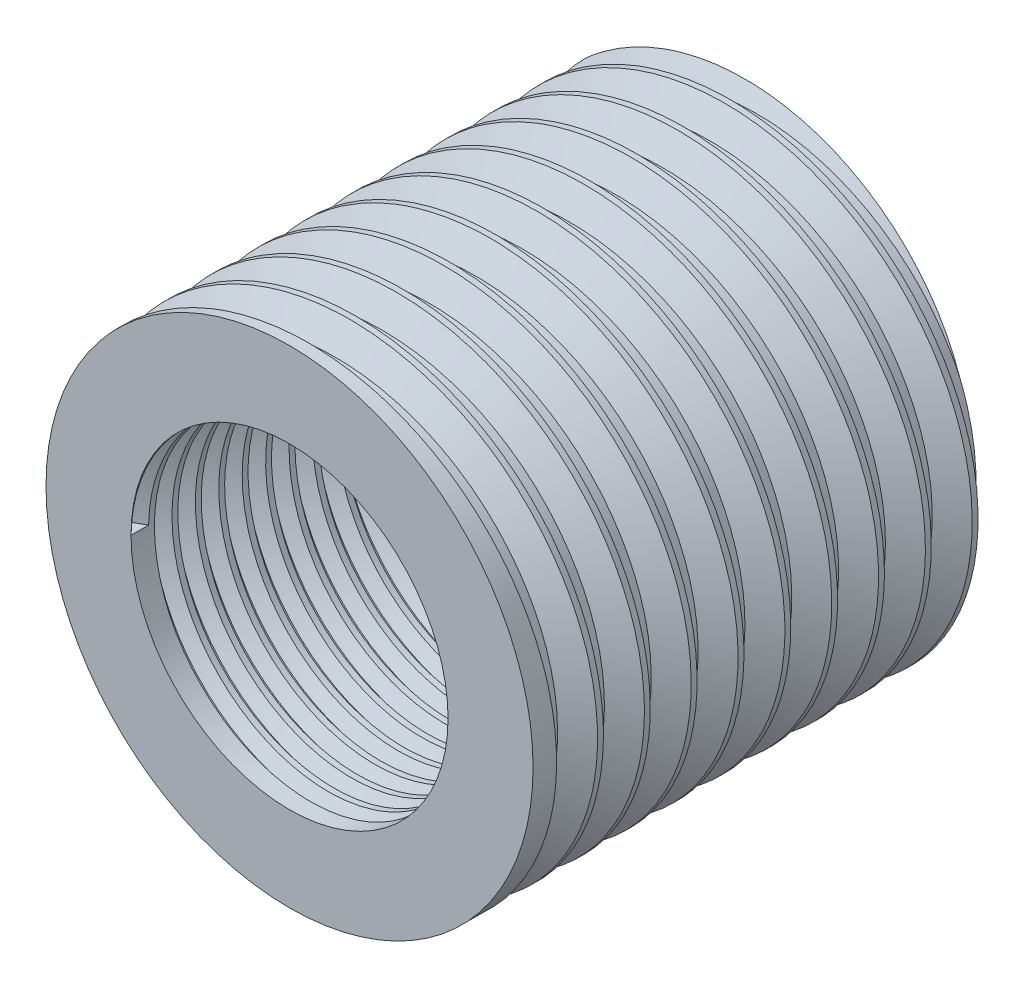
SolidWorks part; units mm, degrees
ref_plane "Front Plane" through (0, 0, 0) normal (0, 0, 1) x (1, 0, 0)
ref_plane "Top Plane" through (0, 0, 0) normal (0, 1, 0) x (1, 0, 0)
ref_plane "Right Plane" through (0, 0, 0) normal (1, 0, 0) x (0, 0, -1)
sketch "Sketch1" plane through (0, 0, 0) normal (0, 0, 1) x (1, 0, 0)
  circle A0 centre (0, 0) radius 10.4
  circle A1 centre (0, 0) radius 6.7693
  dimension "D1" = 20.8
extrude "Boss-Extrude1" add sketch "Sketch1" along normal blind 20
thread "Thread1" pitch 1 method cut profile "Thread Profile1" start angle 0, offset 0, length 20, pitch 1, diameter 13.5386
ref_plane "Plane1" through (-6.7693, 0, 20) normal (0, -1, 0) x (-1, 0, 0)
sketch "Thread Profile1" plane through (-6.7693, 0, 20) normal (0, -1, 0) x (-1, 0, 0)
  line L0 (0, 0) -> (0, 1) construction
  line L1 (0, 0) -> (0.5413, 0.3125)
  line L2 (0.5413, 0.3125) -> (0.5413, 0.4375)
  line L3 (0.5413, 0.4375) -> (0, 0.75)
  line L4 (0.5413, 0.375) -> (0, 0.375) construction
  line L11 (0, 0) -> (0, 0.75)
  point P2 (0, 0)
  dimension "Pitch" = 1
  dimension "Profile_Angle" = 60
  dimension "Profile_Land" = 0.125
  dimension "Profile_Height" = 0.5413
thread "Thread2" pitch 2 method cut profile "Thread Profile2" start angle 0, offset 0, length 20, pitch 2, diameter 20.8
ref_plane "Plane2" through (-10.4, 0, 20) normal (0, -1, 0) x (-1, 0, 0)
sketch "Thread Profile2" plane through (-10.4, 0, 20) normal (0, -1, 0) x (-1, 0, 0)
  line L0 (0, 0) -> (0, 2) construction
  line L11 (0, 0) -> (0, 1.75)
  line L12 (0, 1.75) -> (-1.0825, 1.125)
  line L13 (-1.0825, 1.125) -> (-1.0825, 0.625)
  line L15 (-1.0825, 0.625) -> (0, 0)
  line L17 (-1.0825, 0.875) -> (0, 0.875) construction
  point P2 (0, 0)
  dimension "Pitch" = 2
  dimension "Profile_Angle" = 60
  dimension "Profile_Land" = 0.5
  dimension "Profile_Height" = 1.0825
